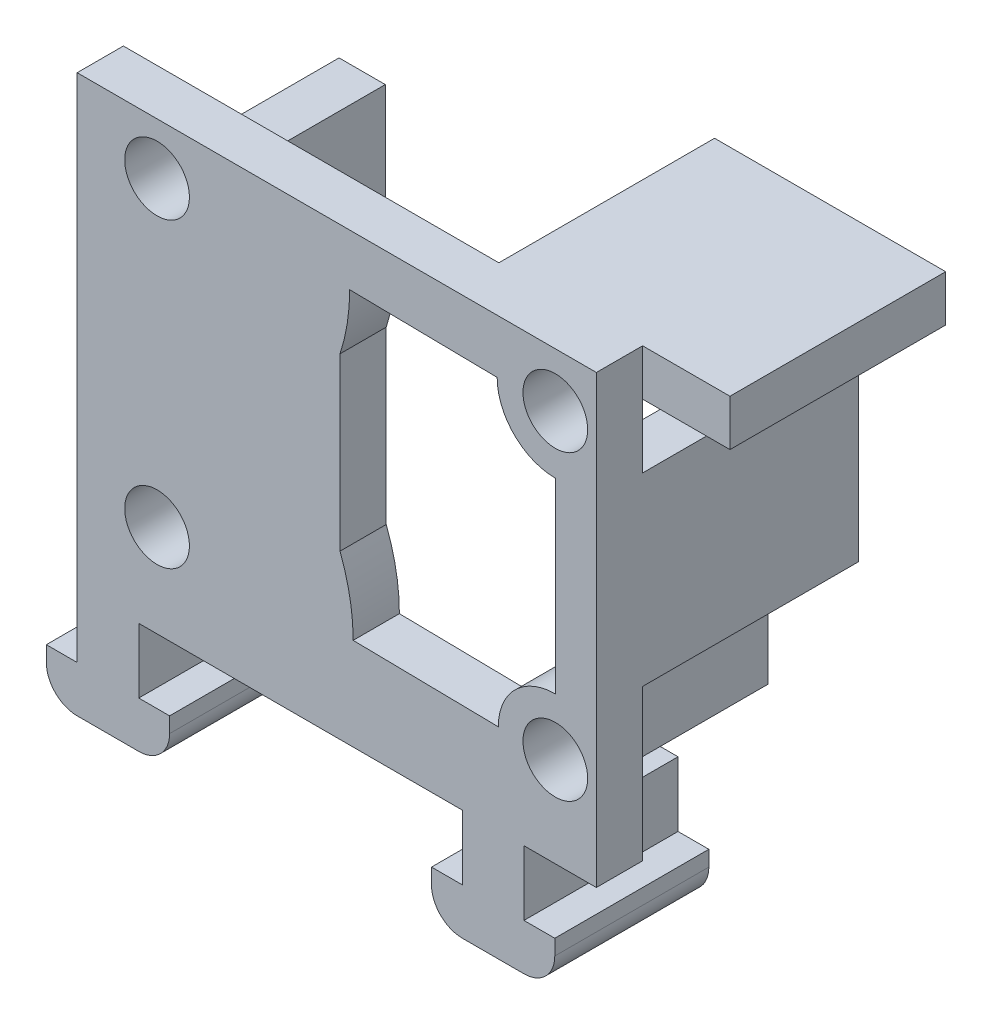
SolidWorks part; units mm, degrees
ref_plane "Спереди" through (0, 0, 0) normal (0, 0, 1) x (1, 0, 0)
ref_plane "Сверху" through (0, 0, 0) normal (0, 1, 0) x (1, 0, 0)
ref_plane "Справа" through (0, 0, 0) normal (1, 0, 0) x (0, 0, -1)
sketch "Эскиз2" plane through (0, 0, 0) normal (0, 0, 1) x (1, 0, 0)
  line L0 (-17.0598, 0) -> (-17.0598, -2.25)
  line L1 (16.6402, 26.7) -> (-17.0598, 26.7)
  line L2 (16.6402, 26.7) -> (16.6402, 0)
  line L4 (-17.0598, 26.7) -> (-17.0598, 0)
  line L5 (-17.0598, -2.25) -> (16.6402, -2.25)
  line L6 (16.6402, -2.25) -> (16.6402, 0)
  line L7 (16.6402, 26.7) -> (30.9983, 26.7) construction
  line L8 (-11.8732, 23.3473) -> (-11.9093, 26.7) construction
  line L9 (-11.8732, 23.3473) -> (-17.0598, 23.3473) construction
  line L10 (0, 19.4273) -> (0, 8.3348)
  line L11 (13.9746, 19.4273) -> (13.9746, 7.303)
  line L12 (0.8545, 3.75) -> (10.2732, 3.6015)
  line L13 (-17.0598, 26.7) -> (-11.9093, 26.7) construction
  line L14 (10.2006, 23.2014) -> (0.6303, 23.3473)
  circle A0 centre (13.9746, 3.6015) radius 2.1
  circle A1 centre (13.9746, 23.2014) radius 2.1
  circle A2 centre (-11.8732, 23.3473) radius 2.1
  circle A3 centre (-11.8732, 3.75) radius 2.1
  arc A4 (13.9746, 7.303) -> (10.2732, 3.6015) centre (13.9746, 3.6015) ccw
  arc A5 (10.2006, 23.2014) -> (13.9746, 19.4273) centre (13.9746, 23.2014) ccw
  arc A6 (0, 19.4273) -> (0.6303, 23.3473) centre (-11.8732, 23.3473) ccw
  arc A7 (0.8545, 3.75) -> (0, 8.3348) centre (-11.8732, 3.75) ccw
  point P12 (30.9983, 21.5985)
  point P13 (30.9983, 4.9988)
  point P14 (30.9983, 1.9985)
  point P15 (30.9983, 24.5985)
  point P16 (32.4984, 3.4986)
  point P25 (5.1505, 21.4035)
  point P26 (5.1505, 24.4965)
  dimension "D1" = 26.7
  dimension "D3" = 4.2
  dimension "D4" = 4.2
  dimension "D5" = 4.2
  dimension "D6" = 4.2
  dimension "D2" = 33.7
  dimension "D7" = 3.3529
  dimension "D8" = 5.1866
extrude "Бобышка-Вытянуть1" add sketch "Эскиз2" along normal blind 2 and the other way blind 1
sketch "Эскиз10" plane through (0, 0, -1) normal (0, 0, -1) x (-1, 0, 0)
  line L0 (-16.6402, 0.75) -> (-22.3105, 0.75) construction
  line L1 (-22.3105, 0.75) -> (-22.3105, 23.7) construction
  line L2 (14.0598, 3.3527) -> (-7.3105, 3.3527) construction
  line L3 (-7.3105, 3.3527) -> (-7.3105, 23.7) construction
  line L9 (-16.6402, 26.7) -> (17.0598, 26.7) construction
  line L10 (-22.3105, 23.7) -> (-7.3105, 23.7)
  line L11 (-22.3105, 23.7) -> (-22.3105, 26.7)
  line L12 (-22.3105, 26.7) -> (-7.3105, 26.7)
  line L13 (-7.3105, 23.7) -> (-7.3105, 26.7)
  line L14 (-16.6402, 0.75) -> (-16.6402, 7.5529) construction
  line L15 (-16.6402, 23.0985) -> (-16.6402, 19.5529) construction
  line L17 (-16.6402, 7.5529) -> (-13.6402, 7.5529)
  line L18 (-16.6402, 7.5529) -> (-16.6402, 19.5529)
  line L19 (-16.6402, 19.5529) -> (-13.6402, 19.5529)
  line L20 (-13.6402, 7.5529) -> (-13.6402, 19.5529)
  line L21 (14.0598, 7.5529) -> (14.0598, 19.0325) construction
  line L22 (17.0598, 26.7) -> (17.0598, -2.25) construction
  line L23 (14.0598, 7.5529) -> (17.0598, 7.5529)
  line L24 (14.0598, 7.5529) -> (14.0598, 19.0325)
  line L25 (14.0598, 19.0325) -> (17.0598, 19.0325)
  line L26 (17.0598, 7.5529) -> (17.0598, 19.0325)
  line L27 (-16.6402, -2.25) -> (-16.6402, 26.7) construction
  dimension "D1" = 15
  dimension "D2" = 12
  dimension "D3" = 3
  dimension "D4" = 3
  dimension "D6" = 3
extrude "Бобышка-Вытянуть4" add sketch "Эскиз10" along normal blind 14
sketch "Sketch1" plane through (0, 0, 2) normal (0, 0, 1) x (1, 0, 0)
  line L0 (-13.0598, -6.45) -> (-11.0598, -6.45)
  line L1 (-17.0598, -2.25) -> (-13.0598, -2.25)
  line L2 (-17.0598, -2.25) -> (-17.0598, -6.45)
  line L3 (-17.0598, -6.45) -> (-13.0598, -6.45)
  line L4 (-13.0598, -2.25) -> (-13.0598, -6.45)
  line L5 (-11.0598, -6.45) -> (-11.0598, -7.45)
  line L6 (-13.0598, -9.45) -> (-17.0598, -9.45)
  line L7 (-15.0598, -2.25) -> (-15.0598, -9.45) construction
  line L8 (-17.0598, -6.45) -> (-19.0598, -6.45)
  line L9 (-19.0598, -6.45) -> (-19.0598, -7.45)
  arc A0 (-11.0598, -7.45) -> (-13.0598, -9.45) centre (-13.0598, -7.45) cw
  arc A1 (-19.0598, -7.45) -> (-17.0598, -9.45) centre (-17.0598, -7.45) ccw
  point P11 (-11.0598, -9.45)
  line M12 (-17.0598, -2.25) -> (16.6402, -2.25)
  dimension "D5" = 2
  dimension "D1" = 4
  dimension "D2" = 4.2
  dimension "D3" = 3
  dimension "D4" = 4
extrude "Boss-Extrude1" add sketch "Sketch1" against normal blind 10 contours L7 L3 L8 L9 A1 L6 | L3 L7 L6 A0 L5 L0 | L1 L7 L3 L4 | L7 L2 L3 M12 region at (-13.1795, -7.8689, 2) region at (-14.0598, -4.35, 2) region at (-16.9402, -7.8689, 2) region at (-16.0598, -4.35, 2)
pattern_linear "LPattern1" count 2 spacing 25 along (1, 0, 0) of "Boss-Extrude1"
sketch "Sketch2" plane through (0, 0, -1) normal (0, 0, -1) x (-1, 0, 0)
  line L0 (13.0598, -2.25) -> (-7.9402, -2.25) construction
  line L1 (-10.7836, -2.25) -> (-7.7836, -2.25)
  line L2 (-10.7836, -2.25) -> (-10.7836, 1.75)
  line L3 (-10.7836, 1.75) -> (-7.7836, 1.75)
  line L4 (-7.7836, -2.25) -> (-7.7836, 1.75)
  dimension "D1" = 4
  dimension "D2" = 3
extrude "Boss-Extrude2" add sketch "Sketch2" along normal blind 14 contours L2 L3 L4 L1
sketch "Sketch3" plane through (7.9402, 0, 0) normal (-1, 0, 0) x (0, 0, 1)
  line L0 (-4.5, -2.25) -> (-1, -2.25)
  line L1 (-8, -2.25) -> (-1, -2.25) construction
  line L2 (-1, -2.25) -> (-1, 0.5589)
  line L3 (-1, 0.5589) -> (-4.5, -2.25)
extrude "Boss-Extrude3" add sketch "Sketch3" against normal blind 4
pattern_linear "LPattern2" count 2 spacing 25 along (-1, 0, 0) of "Boss-Extrude3"
